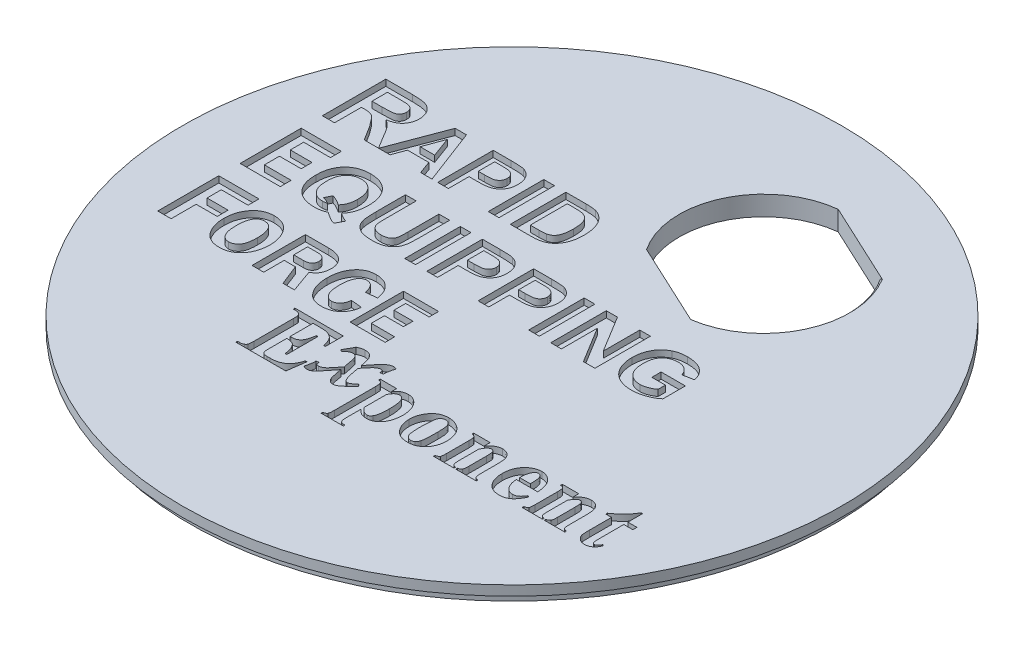
SolidWorks part; units mm, degrees
material "6061 Alloy"
ref_plane "Front Plane" through (0, 0, 0) normal (0, 0, 1) x (1, 0, 0)
ref_plane "Top Plane" through (0, 0, 0) normal (0, 1, 0) x (1, 0, 0)
ref_plane "Right Plane" through (0, 0, 0) normal (1, 0, 0) x (0, 0, -1)
sketch "Sketch1" plane through (0, 0, 0) normal (0, 1, 0) x (1, 0, 0)
  circle A0 centre (0, 0) radius 20.828
  dimension "D1" = 41.656
extrude "Boss-Extrude1" add sketch "Sketch1" along normal blind 1.27
sketch "Sketch2" plane through (0, 1.27, 0) normal (0, 1, 0) x (1, 0, 0)
  circle A0 centre (0, 0) radius 20.32
  circle A1 centre (0, 0) radius 20.828
  circle A2 centre (0, 0) radius 20.828 construction
  dimension "D1" = 0.508
extrude "Cut-Extrude2" cut sketch "Sketch2" against normal blind 0.635
sketch "Sketch3" plane through (0, 1.27, 0) normal (0, 1, 0) x (1, 0, 0)
  line L0 (-8.2448, 26.8258) -> (32.8471, 7.6643) construction
  line L1 (0, 0) -> (8.8023, 18.8766) construction
  line L2 (4.5821, 16.5355) -> (9.7216, 14.1389)
  line L3 (0.6372, 8.0756) -> (5.7766, 5.679)
  arc A0 (5.7766, 5.679) -> (9.7216, 14.1389) centre (5.1794, 11.1073) ccw
  circle A1 centre (0, 0) radius 20.828 construction
  arc A2 (4.5821, 16.5355) -> (0.6372, 8.0756) centre (5.1794, 11.1073) ccw
  circle A3 centre (0, 0) radius 20.32 construction
  point P1 (20.32, 0)
  dimension "D1" = 10.922
  dimension "D3" = 4.6672
  dimension "D4" = 65
  dimension "D2" = 12.2555
extrude "Cut-Extrude3" cut sketch "Sketch3" against normal through all
chamfer "Chamfer1" distance 0.127 angle 45 1 edges at (10.1287, 1.27, -8.7993)
sketch "Sketch13" plane through (0, 0, 0) normal (0, -1, 0) x (1, 0, 0)
  line L0 (8.4392, 17.0695) -> (5.3418, 18.2771)
  line L1 (-5.0512, 24.3244) -> (0.5277, 22.1493) construction
  line L2 (7.5658, 19.4053) -> (0, 0) construction
  arc A0 (5.3418, 18.2771) -> (8.4392, 17.0695) centre (5.9079, 15.153) ccw
  circle A1 centre (0, 0) radius 20.828 construction
  point P10 (5.1794, -11.1073)
  dimension "D3" = 6.35
  dimension "D4" = 2.7051
  dimension "D1" = 16.2639
  dimension "D2" = 133.7
extrude "Cut-Extrude5" cut sketch "Sketch13" against normal through all
sketch "Sketch12" plane through (0, 0, 0) normal (0, -1, 0) x (1, 0, 0)
  line L0 (-10.2147, -4.2027) -> (-10, -4.6631) construction
  line L1 (-19.7462, 0.4611) -> (-7.6606, 6.0967)
  line L2 (-20.514, -1.6486) -> (-14.8784, -13.7342)
  line L3 (-12.7688, -14.502) -> (-0.6831, -8.8664)
  line L4 (-5.5509, 5.3289) -> (0.0847, -6.7568)
  line L5 (-21.185, -0.2098) -> (0.7556, -8.1955) construction
  line L6 (-14.2075, -15.1729) -> (-6.2218, 6.7676) construction
  line L8 (0, 0) -> (-10, -4.6631) construction
  arc A0 (-20.514, -1.6486) -> (-19.7462, 0.4611) centre (-19.0753, -0.9777) cw
  arc A1 (-12.7688, -14.502) -> (-14.8784, -13.7342) centre (-13.4397, -13.0633) cw
  arc A2 (0.0847, -6.7568) -> (-0.6831, -8.8664) centre (-1.3541, -7.4277) cw
  arc A3 (-5.5509, 5.3289) -> (-7.6606, 6.0967) centre (-6.9897, 4.658) ccw
  point P0 (-10.2147, -4.2027)
  point P3 (-10, -4.6631)
  point P22 (5.9079, 15.153)
  point P23 (5.1794, -11.1073)
  dimension "D3" = 16.51
  dimension "D4" = 1.5875
  dimension "D1" = 90
  dimension "D2" = 25.1908
  dimension "D5" = 0.508
  dimension "D6" = 10
extrude "Cut-Extrude4" cut sketch "Sketch12" against normal blind 0.508
sketch "Sketch16" plane through (0, 1.27, 0) normal (0, 1, 0) x (1, 0, 0)
  line L0 (-17.78, 5.08) -> (-17.78, -0.254) construction
  line L1 (-17.78, -0.254) -> (-17.78, -5.588) construction
  text T0 "R" font "Arial" height in points 16
  text T1 "E" font "Franklin Gothic Medium" height in points 16
  text T2 "F" font "Franklin Gothic Medium" height in points 16
  text T3 "APID" font "Arial" height in points 14
  text T4 "QUIPPING" font "Arial" height in points 14
  text T5 "ORCE" font "Franklin Gothic Medium" height in points 14
  text T6 "E  ponent" font "Times New Roman" height in points 16
  text T7 "x" font "Palatino Linotype" height in points 16
  dimension "D1" = 4.064
  dimension "D2" = 5.334
  dimension "D3" = 17.78
  dimension "D4" = 5.08
  dimension "D5" = 3.302
  dimension "D6" = 2.794
  dimension "D7" = 7.62
  dimension "D8" = 10.414
  dimension "D9" = 3.81
  dimension "D10" = 0.889
extrude "Cut-Extrude7" cut sketch "Sketch16" against normal offset from surface (0.4064 mm away) 0.3556 up to face at (-10.2147, 0.508, -4.2027)
sketch "Sketch17" plane through (0, 1.27, 0) normal (0, 1, 0) x (1, 0, 0)
  circle A0 centre (0, 0) radius 21.336
  circle A1 centre (0, 0) radius 20.32
  circle A3 centre (0, 0) radius 20.32 construction
  dimension "D1" = 42.672
extrude "Boss-Extrude3" add sketch "Sketch17" against normal up to surface (0.635 mm away) up to face at (0, 0.635, 20.32)
sketch "Sketch18" plane through (0, 0, 0) normal (0, -1, 0) x (1, 0, 0)
  line L0 (-20.514, -1.6486) -> (-14.8784, -13.7342) construction
  line L1 (-7.6606, 6.0967) -> (-19.7462, 0.4611) construction
  line L2 (-19.8414, -3.091) -> (-19.7099, 0.478)
  arc A0 (-20.7939, 1.1686) -> (-19.7099, 0.478) centre (-20.0319, 1.1686) ccw
  arc A1 (-19.8414, -3.091) -> (-20.5629, -3.3126) centre (-20.1867, -3.252) ccw
  circle A2 centre (0, 0) radius 20.828 construction
  arc A3 (-20.7939, 1.1686) -> (-20.5629, -3.3126) centre (-15.0513, -0.7819) ccw
  point P10 (-19.7099, 0.478)
  point P11 (-19.8414, -3.091)
  point P12 (-20.7926, 1.213)
  point P13 (-20.5629, -3.3126)
  dimension "D1" = 1.524
  dimension "D2" = 0.762
  dimension "D3" = 6.0648
extrude "Cut-Extrude14" cut sketch "Sketch18" against normal up to surface (0.508 mm away) up to face at (-10.2147, 0.508, -4.2027)
sketch "Sketch19" plane through (0, 1.27, 0) normal (0, 1, 0) x (1, 0, 0)
  circle A0 centre (5.9079, -15.153) radius 3.175
  arc A1 (8.4392, -17.0695) -> (5.3418, -18.2771) centre (5.9079, -15.153) ccw construction
extrude "Boss-Extrude4" add sketch "Sketch19" against normal up to surface (1.27 mm away) up to face at (5.8225, 0, 14.9341)
